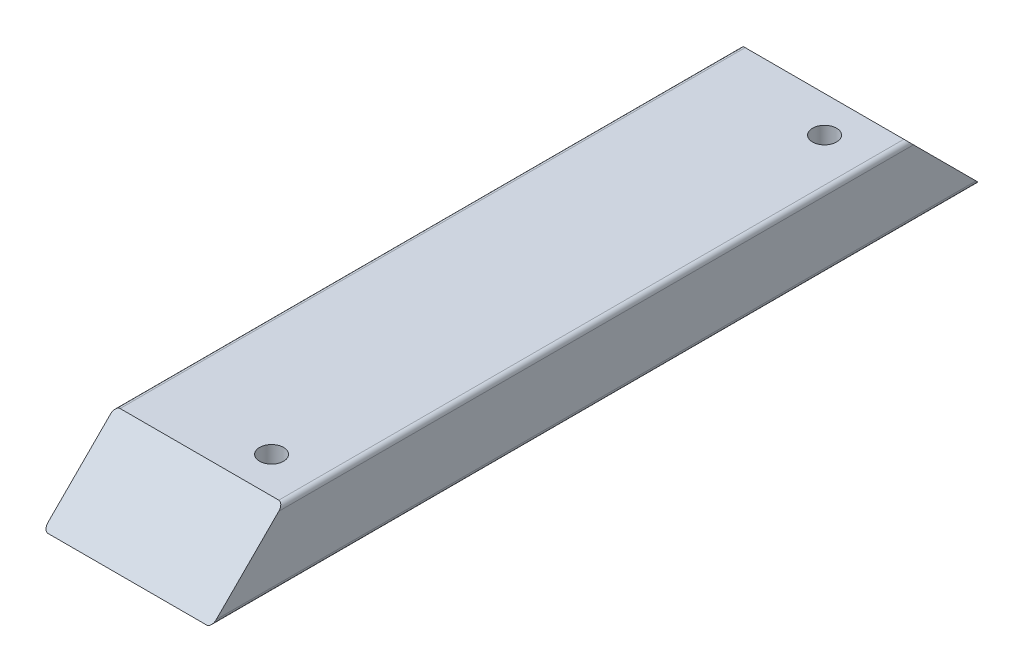
SolidWorks part; units mm, degrees
ref_plane "Front Plane" through (0, 0, 0) normal (0, 0, 1) x (1, 0, 0)
ref_plane "Top Plane" through (0, 0, 0) normal (0, 1, 0) x (1, 0, 0)
ref_plane "Right Plane" through (0, 0, 0) normal (1, 0, 0) x (0, 0, -1)
sketch "Sketch1" plane through (0, 0, 0) normal (0, 0, 1) x (1, 0, 0)
  line L1 (-44.45, 19.05) -> (44.45, 19.05)
  line L2 (-44.45, 19.05) -> (-44.45, -19.05)
  line L3 (-44.45, -19.05) -> (44.45, -19.05)
  line L4 (44.45, 19.05) -> (44.45, -19.05)
  line L5 (-44.45, 19.05) -> (44.45, -19.05) construction
  line L6 (-44.45, -19.05) -> (44.45, 19.05) construction
  point P0 (0, 0)
  dimension "D1" = 88.9
  dimension "D2" = 38.1
extrude "Boss-Extrude1" add sketch "Sketch1" along normal blind 406.4
fillet "Fillet1" radius 2.54 4 edges at (-44.45, -19.05, 203.2) (44.45, -19.05, 203.2) (44.45, 19.05, 203.2) (-44.45, 19.05, 203.2)
sketch "Sketch2" plane through (-44.45, 0, 0) normal (-1, 0, 0) x (0, 0, 1)
  line L0 (0, 19.05) -> (0, -19.05)
  line L1 (406.4, -19.05) -> (0, -19.05) construction
  line L2 (0, -16.51) -> (0, -19.05) construction
  line L3 (0, -19.05) -> (38.1, 19.05)
  line L4 (0, 19.05) -> (406.4, 19.05) construction
  line L5 (38.1, 19.05) -> (0, 19.05)
  dimension "D1" = 45
extrude "Cut-Extrude1" cut sketch "Sketch2" against normal blind 406.4
ref_plane "Plane1" through (0, 0, 203.2) normal (0, 0, 1) x (1, 0, 0)
mirror "Mirror1" about plane through (0, 0, 203.2) normal (0, 0, 1) of "Cut-Extrude1"
sketch "Sketch3" plane through (0, 19.05, 0) normal (0, 1, 0) x (1, 0, 0)
  line L1 (41.91, -38.1) -> (-41.91, -38.1) construction
  line L2 (44.45, -35.56) -> (44.45, -370.84) construction
  circle A0 centre (19.05, -57.15) radius 6.35
  dimension "D2" = 12.7
  dimension "D1" = 25.4
  dimension "D3" = 19.05
extrude "Cut-Extrude2" cut sketch "Sketch3" against normal blind 406.4
mirror "Mirror2" about plane through (0, 0, 203.2) normal (0, 0, 1) of "Cut-Extrude2"
